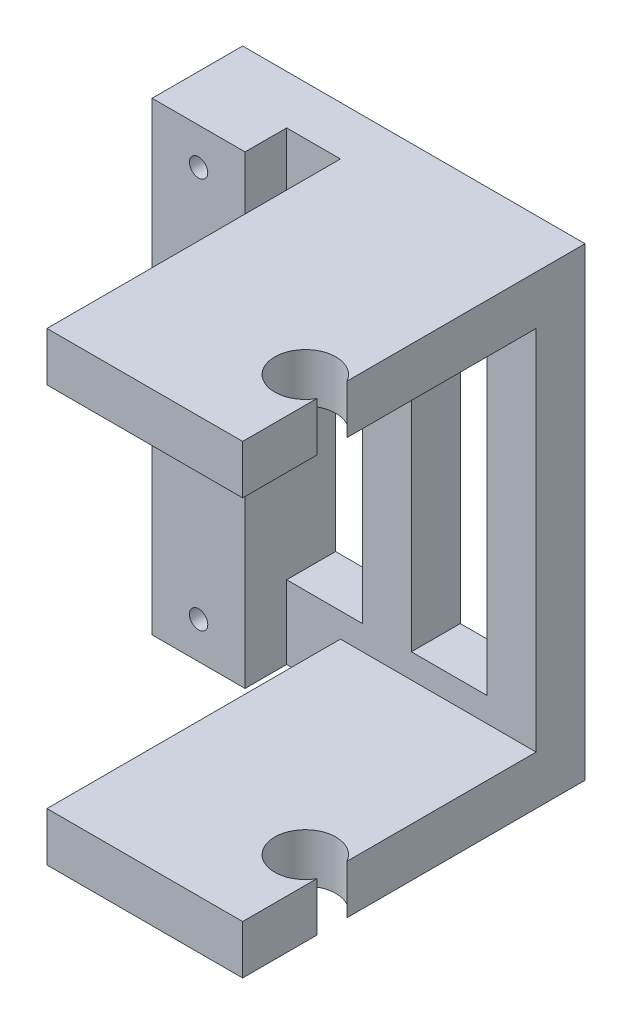
SolidWorks part; units mm, degrees
ref_plane "前视基准面" through (0, 0, 0) normal (0, 0, 1) x (1, 0, 0)
ref_plane "上视基准面" through (0, 0, 0) normal (0, 1, 0) x (1, 0, 0)
ref_plane "右视基准面" through (0, 0, 0) normal (1, 0, 0) x (0, 0, -1)
sketch "草图2" plane through (0, 0, 0) normal (0, 0, 1) x (1, 0, 0)
  line L3 (-7.9, -9.5) -> (6.1, -9.5)
  line L4 (6.1, 9.5) -> (6.1, -9.5)
  line L5 (0, 0) -> (2.4933, 0) construction
  line L6 (0, 0) -> (0, -3.9686) construction
  line L15 (-7.9, 9.5) -> (6.1, 9.5)
  line L16 (-4.1, 6.5) -> (-1, 6.5)
  line L17 (-4.1, 6.5) -> (-4.1, -6.5)
  line L18 (-4.1, -6.5) -> (-1, -6.5)
  line L20 (-7.9, 9.5) -> (-7.9, -9.5)
  line L21 (1, 6.5) -> (4.1, 6.5)
  line L23 (1, -6.5) -> (1, 6.5)
  line L25 (-1, -6.5) -> (-1, 6.5)
  line L26 (4.1, 6.5) -> (4.1, -6.5)
  line L28 (1, -6.5) -> (4.1, -6.5)
  point P0 (0, 0)
  dimension "D1" = 14
  dimension "D3" = 19
  dimension "D4" = 3.8
  dimension "D5" = 3
  dimension "D6" = 2
  dimension "D8" = 3
  dimension "D9" = 2
extrude "凸台-拉伸1" add sketch "草图2" along normal blind 2
sketch "草图3" plane through (0, 0, 2) normal (0, 0, 1) x (1, 0, 0)
  line L1 (-1.9, 9.5) -> (6.1, 9.5)
  line L2 (-1.9, 9.5) -> (-1.9, 7.5)
  line L3 (-1.9, 7.5) -> (6.1, 7.5)
  line L4 (6.1, 9.5) -> (6.1, 7.5)
  line L5 (6.1, -9.5) -> (6.1, 9.5) construction
  line L6 (-1.9, -7.5) -> (6.1, -7.5)
  line L8 (-1.9, -9.5) -> (6.1, -9.5)
  line L9 (6.1, -7.5) -> (6.1, -9.5)
  line L10 (-7.9, -9.5) -> (6.1, -9.5) construction
  line L11 (-1.9, -7.5) -> (-1.9, -9.5)
  line L12 (6.1, 9.5) -> (-7.9, 9.5) construction
  dimension "D1" = 2
  dimension "D2" = 2
  dimension "D3" = 8
  dimension "D4" = 8
extrude "凸台-拉伸2" add sketch "草图3" along normal blind 12
sketch "草图10" plane through (0, 0, 2) normal (0, 0, 1) x (1, 0, 0)
  line L0 (-7.9, 9.5) -> (-7.9, -9.5) construction
  line L1 (-7.9, 9.5) -> (-4.1, 9.5)
  line L2 (-7.9, 9.5) -> (-7.9, -9.5)
  line L3 (-7.9, -9.5) -> (-4.1, -9.5)
  line L4 (-4.1, 9.5) -> (-4.1, -9.5)
  line L5 (-1.9, 9.5) -> (-7.9, 9.5) construction
  line L6 (-7.9, -9.5) -> (-1.9, -9.5) construction
  line L7 (-4.1, 6.5) -> (-4.1, -6.5) construction
extrude "凸台-拉伸4" add sketch "草图10" along normal blind 1.7
sketch "草图9" plane through (0, 0, 2) normal (0, 0, 1) x (1, 0, 0)
  line L0 (-1.9, 9.5) -> (-4.1, 9.5) construction
  line L1 (-7.9, 9.5) -> (-7.9, -9.5) construction
  line L2 (-4.1, -9.5) -> (-1.9, -9.5) construction
  circle A0 centre (-6, 8) radius 0.375
  circle A1 centre (-6, -8) radius 0.375
  dimension "D1" = 0.75
  dimension "D2" = 0.75
  dimension "D3" = 1.5
  dimension "D4" = 1.9
  dimension "D5" = 1.5
  dimension "D6" = 1.9
extrude "切除-拉伸2" cut sketch "草图9" against normal up to next from surface starting at face at (-6, 0, 3.7)
sketch "草图11" plane through (0, -9.5, 0) normal (0, -1, 0) x (1, 0, 0)
  circle A0 centre (5.0135, 10.3506) radius 1.25
  dimension "D1" = 2.5
extrude "切除-拉伸3" cut sketch "草图11" against normal through all
